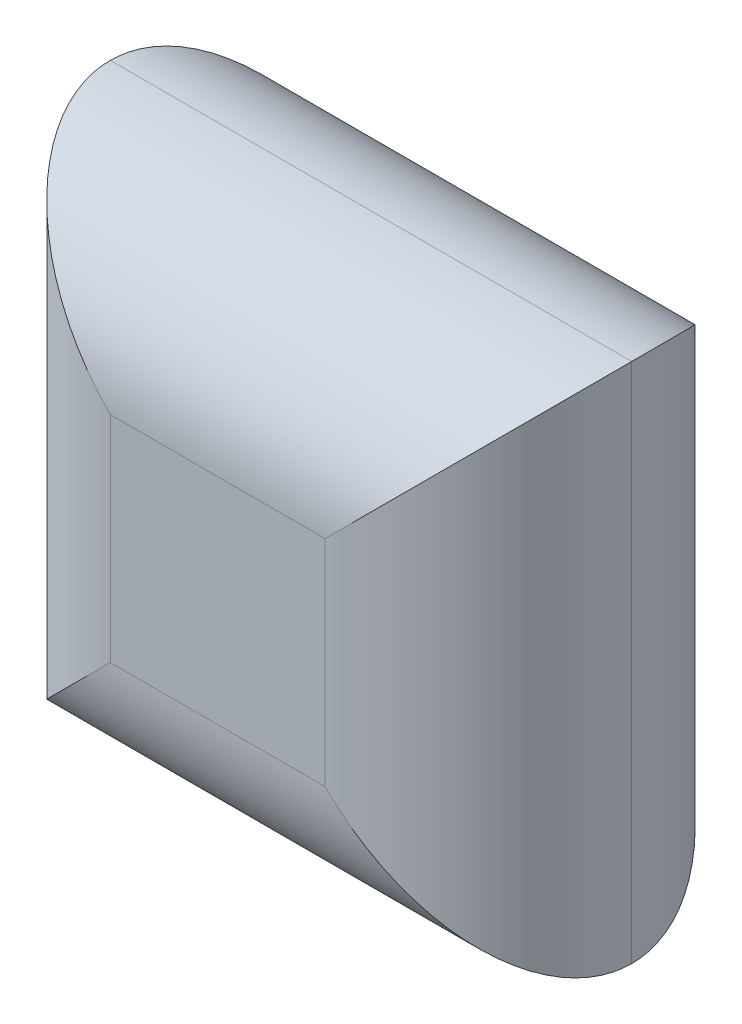
SolidWorks part; units mm, degrees
other "Parachute"
ref_plane "Front Plane" through (0, 0, 0) normal (0, 0, 1) x (1, 0, 0)
ref_plane "Top Plane" through (0, 0, 0) normal (0, 1, 0) x (1, 0, 0)
ref_plane "Right Plane" through (0, 0, 0) normal (1, 0, 0) x (0, 0, -1)
sketch "Sketch1" plane through (0, 0, 0) normal (0, 0, 1) x (1, 0, 0)
  line L1 (0, 0) -> (170, 0)
  line L2 (0, 0) -> (0, 170)
  line L3 (0, 170) -> (170, 170)
  line L4 (170, 0) -> (170, 170)
  dimension "D1" = 170
extrude "Boss-Extrude1" add sketch "Sketch1" along normal blind 100
fillet "Fillet1" radius 50 8 edges at (85, 0, 0) (170, 85, 0) (85, 170, 0) (0, 85, 0) (85, 170, 100) (170, 85, 100) (85, 0, 100) (0, 85, 100)
